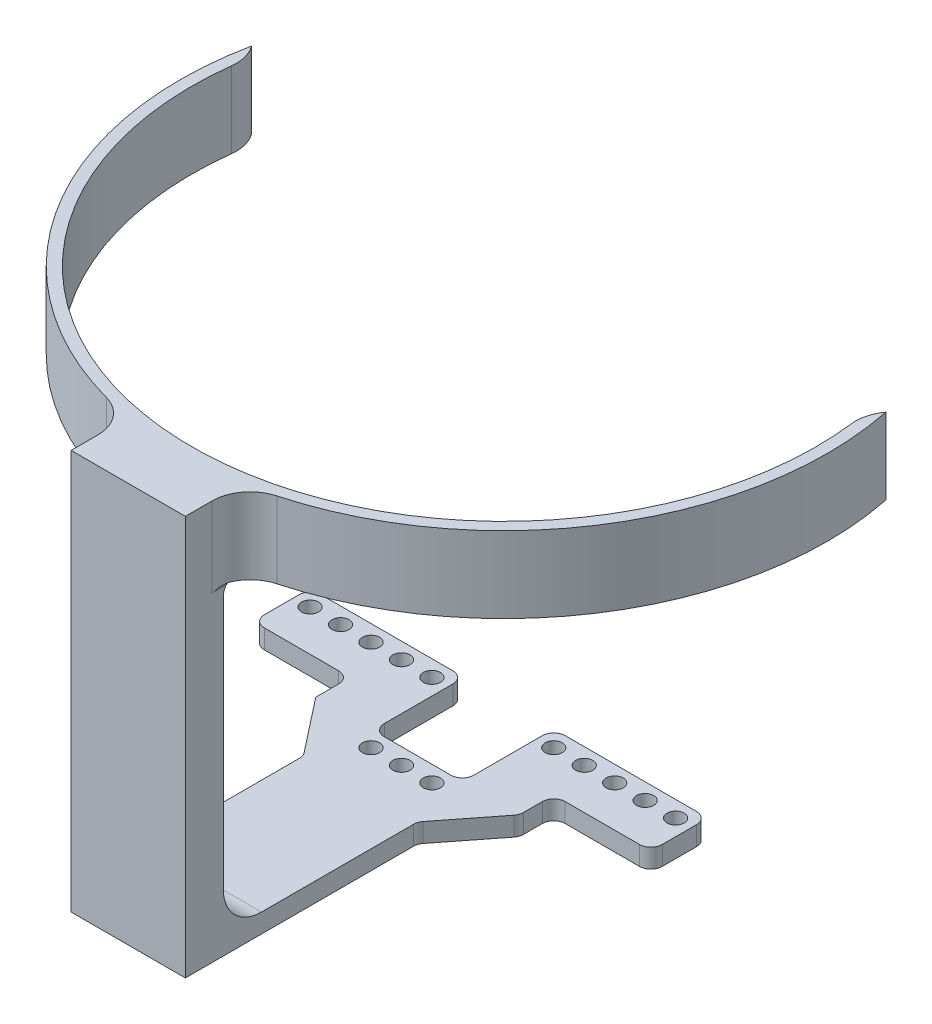
SolidWorks part; units mm, degrees
ref_plane "前视基准面" through (0, 0, 0) normal (0, 0, 1) x (1, 0, 0)
ref_plane "上视基准面" through (0, 0, 0) normal (0, 1, 0) x (1, 0, 0)
ref_plane "右视基准面" through (0, 0, 0) normal (1, 0, 0) x (0, 0, -1)
sketch "草图2" plane through (0, 0, 0) normal (0, 1, 0) x (1, 0, 0)
  line L0 (-48, 45.75) -> (-40, 45.75) construction
  line L1 (-52.25, 50) -> (52.25, 50)
  line L2 (-52.25, 50) -> (-52.25, 35)
  line L4 (52.25, 50) -> (52.25, 35)
  line L5 (-52.25, 50) -> (52.25, -50) construction
  line L6 (-52.25, -50) -> (52.25, 50) construction
  line L7 (0, 50) -> (0, -50) construction
  line L8 (-26.75, 35) -> (-52.25, 35)
  line L9 (-11.75, 26) -> (11.75, 26)
  line L10 (-11.75, 26) -> (-11.75, 50)
  line L11 (-11.75, 50) -> (11.75, 50)
  line L12 (11.75, 26) -> (11.75, 50)
  line L13 (-11.75, 26) -> (11.75, 50) construction
  line L14 (-11.75, 50) -> (11.75, 26) construction
  line L15 (-26.75, 35) -> (-26.75, 26)
  line L17 (26.75, 35) -> (52.25, 35)
  line L21 (-52.25, 35) -> (-52.25, -50) construction
  line L23 (-52.25, -50) -> (52.25, -50) construction
  line L25 (52.25, 35) -> (52.25, -50) construction
  line L27 (-26.75, 26) -> (-26.75, 11) construction
  line L29 (26.75, 35) -> (26.75, 26)
  line L34 (-26.75, 26) -> (-15, 11)
  line L35 (11.495, 11) -> (15, 11) construction
  line L36 (-15, 11) -> (-15, -50)
  line L37 (-15, -50) -> (15, -50)
  line L38 (15, 11) -> (15, -50)
  line L39 (26.75, 26) -> (15, 11)
  line L40 (-15, 11) -> (-11.495, 11) construction
  line L41 (-11.495, 11) -> (0, 11) construction
  line L42 (0, 11) -> (11.495, 11) construction
  circle A0 centre (-48, 45.75) radius 2.25
  circle A1 centre (-40, 45.75) radius 2.25
  circle A2 centre (-32, 45.75) radius 2.25
  circle A3 centre (-24, 45.75) radius 2.25
  circle A4 centre (-16, 45.75) radius 2.25
  circle A5 centre (48, 45.75) radius 2.25
  circle A6 centre (40, 45.75) radius 2.25
  circle A7 centre (32, 45.75) radius 2.25
  circle A8 centre (24, 45.75) radius 2.25
  circle A9 centre (16, 45.75) radius 2.25
  circle A10 centre (-8, 21.75) radius 2.25
  circle A11 centre (0, 21.75) radius 2.25
  circle A13 centre (8, 21.75) radius 2.25
  point P0 (0, 0)
  point P20 (0, 38)
  point P55 (0, -50)
  dimension "D3" = 4.5
  dimension "D4" = 4.25
  dimension "D10" = 4.5
  dimension "D11" = 24
  dimension "D12" = 4.5
  dimension "D13" = 8
  dimension "D1" = 104.5
  dimension "D2" = 100
  dimension "D5" = 4.25
  dimension "D7" = 8
  dimension "D8" = 4.25
  dimension "D9" = 4.25
  dimension "D14" = 15
  dimension "D15" = 15
  dimension "D16" = 15
  dimension "D17" = 30
  dimension "D18" = 15
  dimension "D6" = 5
extrude "凸台-拉伸1" add sketch "草图2" along normal blind 5 contours L12 L9 L10 L1 L2 L4 A8 A6 A0 A1 A2 A3 A4 A5 A7 A9 region at (0, 0, -7.4708)
sketch "草图3" plane through (0, 5, 0) normal (0, 1, 0) x (1, 0, 0)
  line L0 (-15, 11) -> (-15, -50) construction
  line L1 (-15, -40) -> (15, -40)
  line L2 (-15, -40) -> (-15, -50)
  line L3 (-15, -50) -> (15, -50)
  line L4 (15, -40) -> (15, -50)
  line L5 (-15, -40) -> (15, -50) construction
  line L6 (-15, -50) -> (15, -40) construction
  point P0 (0, -45)
  dimension "D1" = 10
extrude "凸台-拉伸2" add sketch "草图3" along normal blind 80
sketch "草图6" plane through (0, 85, 0) normal (0, 1, 0) x (1, 0, 0)
  line L0 (-15, -35) -> (-15, -50)
  line L1 (-15, 11) -> (-15, -40) construction
  line L2 (-15, -50) -> (15, -50)
  line L3 (15, -50) -> (15, -35)
  line L4 (15, 11) -> (15, -40) construction
  line L5 (-83.2827, 65.666) -> (-80.2185, 65.666)
  line L6 (80.2185, 65.666) -> (83.2827, 65.666)
  arc A0 (-83.2827, 65.666) -> (-15, -35) centre (0, 48.666) ccw
  arc A1 (-80.2185, 65.666) -> (80.2185, 65.666) centre (0, 48.666) ccw
  arc A2 (15, -35) -> (83.2827, 65.666) centre (0, 48.666) ccw
  dimension "D1" = 170
  dimension "D2" = 3
  dimension "D3" = 15
  dimension "D4" = 17
extrude "凸台-拉伸3" add sketch "草图6" along normal blind 20
fillet "圆角1" radius 10 5 edges at (0, 5, 40) (-15, 95, 35) (15, 95, 35) (80.2185, 95, -65.666) (-80.2185, 95, -65.666)
fillet "圆角2" radius 3 14 edges at (52.25, 2.5, -50) (52.25, 2.5, -35) (26.75, 2.5, -35) (26.75, 2.5, -26) (15, 2.5, -11) (-15, 2.5, -11) (-26.75, 2.5, -35) (-52.25, 2.5, -35) (-52.25, 2.5, -50) (-11.75, 2.5, -50) (-11.75, 2.5, -26) (11.75, 2.5, -26) (11.75, 2.5, -50) (0, 85, 40)
fillet "圆角3" radius 1 2 edges at (-15, 85, 39.9928) (15, 85, 39.9928)
